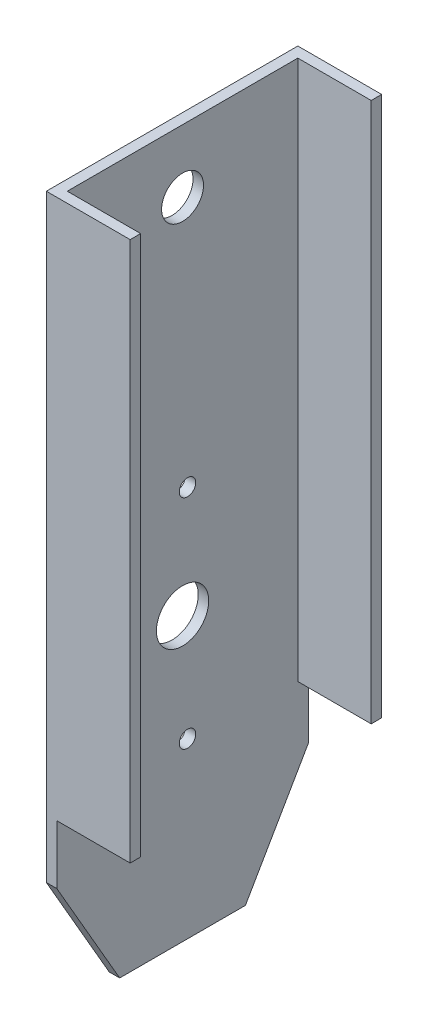
SolidWorks part; units mm, degrees
ref_plane "Front Plane" through (0, 0, 0) normal (0, 0, 1) x (1, 0, 0)
ref_plane "Top Plane" through (0, 0, 0) normal (0, 1, 0) x (1, 0, 0)
ref_plane "Right Plane" through (0, 0, 0) normal (1, 0, 0) x (0, 0, -1)
sketch "Sketch1" plane through (0, 0, 0) normal (0, 1, 0) x (1, 0, 0)
  line L0 (-20.955, 0) -> (-20.955, 38.1)
  line L1 (-20.955, 38.1) -> (4.445, 38.1)
  line L2 (4.445, 38.1) -> (4.445, 34.925)
  line L3 (4.445, 34.925) -> (-17.78, 34.925)
  line L4 (-17.78, 34.925) -> (-17.78, -34.925)
  line L5 (-17.78, -34.925) -> (4.445, -34.925)
  line L6 (4.445, -34.925) -> (4.445, -38.1)
  line L7 (4.445, -38.1) -> (-20.955, -38.1)
  line L8 (-20.955, -38.1) -> (-20.955, 0)
  dimension "D1" = 3.175
  dimension "D2" = 3.175
  dimension "D3" = 3.175
  dimension "D4" = 25.4
  dimension "D5" = 25.4
  dimension "D6" = 38.1
  dimension "D7" = 38.1
extrude "Boss-Extrude1" add sketch "Sketch1" along normal mid plane 214.376
sketch "Sketch2" plane through (0, 0, 38.1) normal (0, 0, 1) x (1, 0, 0)
  line L0 (-17.78, -107.188) -> (-17.78, -56.388)
  line L1 (-20.955, -107.188) -> (4.445, -107.188) construction
  line L2 (-17.78, -56.388) -> (4.445, -56.388)
  line L3 (4.445, 107.188) -> (4.445, -107.188) construction
  line L4 (4.445, -56.388) -> (4.445, -107.188)
  line L5 (4.445, -107.188) -> (-17.78, -107.188)
  line L6 (-20.955, 107.188) -> (-20.955, -107.188) construction
  dimension "D1" = 3.175
  dimension "D2" = 22.225
  dimension "D3" = 50.8
extrude "Cut-Extrude1" cut sketch "Sketch2" against normal blind 208.026
sketch "Sketch3" plane through (-20.955, 0, 0) normal (-1, 0, 0) x (0, 0, 1)
  line L1 (-38.1, -107.188) -> (38.1, -107.188) construction
  circle A0 centre (0, 88.138) radius 6.35
  dimension "D1" = 12.7
  dimension "D2" = 195.326
extrude "Cut-Extrude2" cut sketch "Sketch3" against normal blind 45.974
chamfer "Chamfer1" distance 19.05 angle 60 1 edges at (-19.3675, -107.188, -38.1) first distance on face at (-19.3675, -107.188, 0)
chamfer "Chamfer2" distance 19.05 angle 60 1 edges at (-19.3675, -107.188, 38.1) first distance on face at (-19.3675, -107.188, 9.525)
sketch "Sketch4" plane through (-20.955, 0, 0) normal (-1, 0, 0) x (0, 0, 1)
  line L3 (-38.1, 107.188) -> (-38.1, -74.1924) construction
  circle A0 centre (-1.5, 11.3124) radius 2.5
  circle A1 centre (-1.5, -54.6876) radius 2.5
  circle A2 centre (0, -21.6876) radius 7.9248
  dimension "D4" = 38.1
  dimension "D5" = 5
  dimension "D2" = 15.8496
  dimension "D1" = 66
  dimension "D3" = 33
  dimension "D6" = 1.5
  dimension "D7" = 1.5
extrude "Cut-Extrude3" cut sketch "Sketch4" against normal up to next
